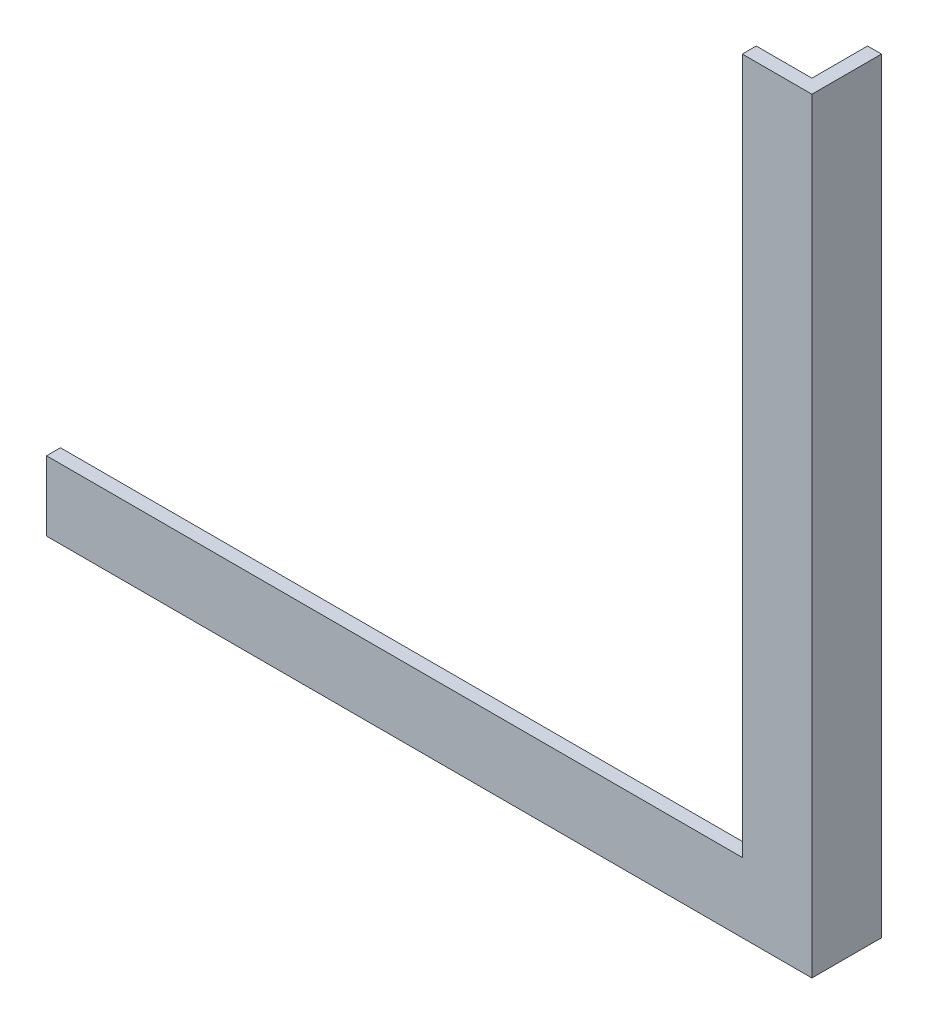
SolidWorks part; units mm, degrees
ref_plane "Front Plane" through (0, 0, 0) normal (0, 0, 1) x (1, 0, 0)
ref_plane "Top Plane" through (0, 0, 0) normal (0, 1, 0) x (1, 0, 0)
ref_plane "Right Plane" through (0, 0, 0) normal (1, 0, 0) x (0, 0, -1)
sketch "Sketch1" plane through (0, 0, 0) normal (0, 0, 1) x (1, 0, 0)
  line L0 (0, 0) -> (0, 150)
  line L1 (0, 150) -> (15, 150)
  line L2 (15, 150) -> (15, -15)
  line L3 (15, -15) -> (-150, -15)
  line L4 (-150, -15) -> (-150, 0)
  line L5 (-150, 0) -> (0, 0)
  dimension "D1" = 15
  dimension "D2" = 15
  dimension "D3" = 150
  dimension "D4" = 150
extrude "Boss-Extrude1" add sketch "Sketch1" along normal blind 15
sketch "Sketch2" plane through (0, 0, 0) normal (0, 0, -1) x (-1, 0, 0)
  line L0 (0, 150) -> (-12, 150)
  line L1 (-15, 150) -> (0, 150) construction
  line L2 (-12, 150) -> (-12, -12)
  line L3 (-12, -12) -> (150, -12)
  line L4 (150, 0) -> (150, -15) construction
  line L5 (150, -12) -> (150, 0)
  line L6 (150, 0) -> (0, 0)
  line L7 (0, 0) -> (0, 150)
  line L8 (-15, -15) -> (-15, 150) construction
  line L9 (150, -15) -> (-15, -15) construction
  dimension "D1" = 3
  dimension "D2" = 3
extrude "Cut-Extrude1" cut sketch "Sketch2" against normal blind 12
